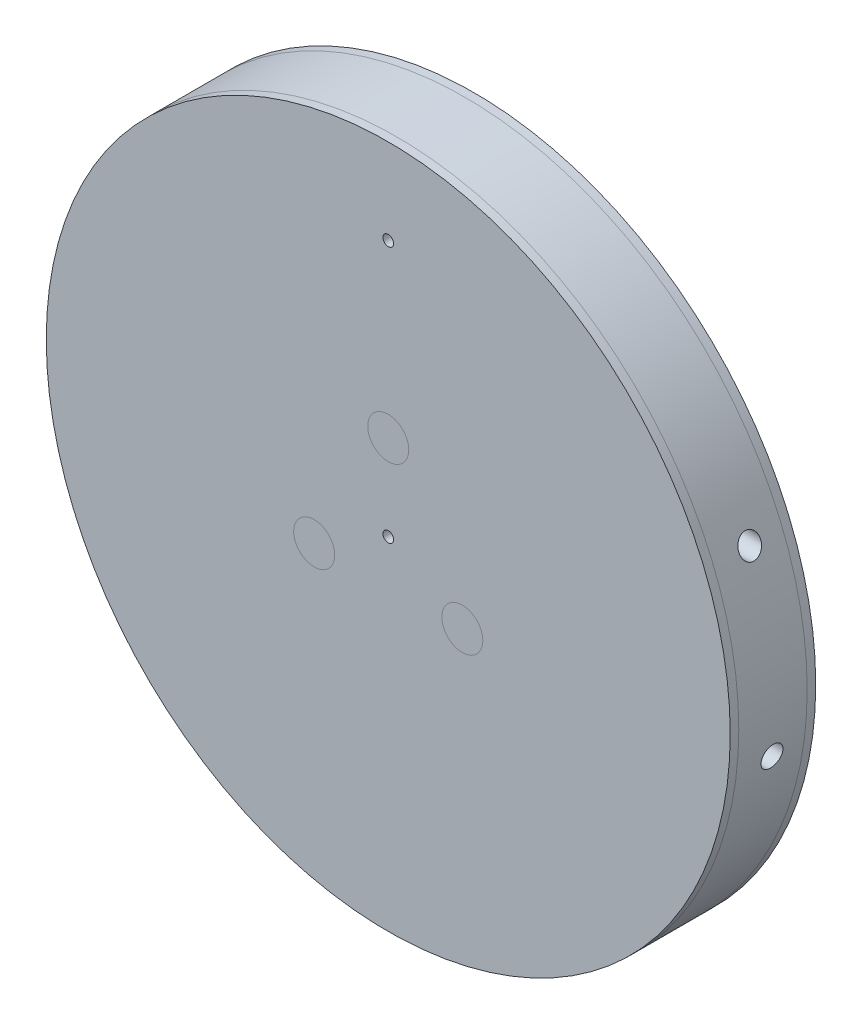
SolidWorks part; units mm, degrees
ref_plane "Front Plane" through (0, 0, 0) normal (0, 0, 1) x (1, 0, 0)
ref_plane "Top Plane" through (0, 0, 0) normal (0, 1, 0) x (1, 0, 0)
ref_plane "Right Plane" through (0, 0, 0) normal (1, 0, 0) x (0, 0, -1)
sketch "Sketch1" plane through (0, 0, 0) normal (0, 0, 1) x (1, 0, 0)
  circle A0 centre (0, 0) radius 100
  dimension "D1" = 200
extrude "Boss-Extrude1" add sketch "Sketch1" along normal blind 25
sketch "Sketch2" plane through (0, 0, 0) normal (1, 0, 0) x (0, 0, -1)
  line L0 (-25, 100) -> (-25, -100) construction
  circle A0 centre (-12, 37.5) radius 3.2
  dimension "D1" = 6.4
  dimension "D2" = 13
  dimension "D3" = 37.5
extrude "Cut-Extrude1" cut sketch "Sketch2" against normal blind 55.2975 and the other way through all
sketch "Sketch3" plane through (0, 0, 0) normal (1, 0, 0) x (0, 0, -1)
  circle A0 centre (-12, -12.5) radius 3.2
  dimension "D1" = 6.4
  dimension "D2" = 12
  dimension "D3" = 12.5
extrude "Cut-Extrude2" cut sketch "Sketch3" along normal through all and the other way blind 54.7843
sketch "Sketch4" plane through (0, 0, 0) normal (1, 0, 0) x (0, 0, -1)
  line L0 (0, -100) -> (0, 100) construction
  circle A0 centre (-12, 12.5) radius 3.2
  dimension "D2" = 6.4
  dimension "D1" = 12
  dimension "D3" = 12.5
extrude "Cut-Extrude3" cut sketch "Sketch4" against normal through all and the other way blind 54.7843
sketch "Sketch5" plane through (0, 0, 0) normal (1, 0, 0) x (0, 0, -1)
  line L0 (0, -100) -> (0, 100) construction
  circle A0 centre (-12, -37.5) radius 3.2
  dimension "D2" = 6.4
  dimension "D1" = 12
  dimension "D3" = 37.5
extrude "Cut-Extrude4" cut sketch "Sketch5" against normal through all and the other way blind 55.2975
sketch "Sketch6" plane through (0, 0, 0) normal (0, 0, -1) x (-1, 0, 0)
  circle A0 centre (0, 0) radius 50
  dimension "D1" = 100
extrude "Boss-Extrude5" add sketch "Sketch6" along normal blind 0.1 separate body
sketch "Sketch8" plane through (0, 0, -0.1) normal (0, 0, -1) x (-1, 0, 0)
  circle A1 centre (0, 0) radius 50
  circle A2 centre (0, 0) radius 50
  dimension "D1" = 0
extrude "Boss-Extrude6" add sketch "Sketch8" along normal blind 0.525 separate body
ref_plane "Bottom Plane" through (0, 0, 25) normal (0, 0, 1) x (1, 0, 0)
sketch "Sketch10" plane through (0, 0, 25) normal (0, 0, 1) x (1, 0, 0)
  circle A0 centre (0, 0) radius 1.55
  dimension "D1" = 3.1
extrude "Cut-Extrude5" cut sketch "Sketch10" against normal blind 21
sketch "Sketch11" plane through (0, 0, 25) normal (0, 0, 1) x (1, 0, 0)
  circle A0 centre (0, 75) radius 1.55
  point P2 (0, 0)
  point P5 (0, 0)
  point P6 (0, 0)
  dimension "D1" = 3.1
  dimension "D2" = 75
extrude "Cut-Extrude6" cut sketch "Sketch11" against normal blind 21
ref_plane "Ref1" through (50, 0, 0) normal (1, 0, 0) x (0, 0, -1)
ref_plane "Ref2" through (-50, 0, 0) normal (1, 0, 0) x (0, 0, -1)
ref_plane "BandRef1" through (0, 0, 2.5) normal (0, 0, 1) x (1, 0, 0)
ref_plane "BandRef2" through (0, 0, 22.5) normal (0, 0, 1) x (1, 0, 0)
split line "Split Line3"
split line "Split Line4"
sketch "Sketch12" plane through (0, 0, 25) normal (0, 0, 1) x (1, 0, 0)
  circle A0 centre (-21.6506, -12.5) radius 6
  circle A1 centre (0, 25) radius 6
  circle A2 centre (21.6506, -12.5) radius 6
  dimension "D1" = 12
  dimension "D4" = 12
  dimension "D5" = 12
  dimension "D2" = 25
  dimension "D3" = 25
  dimension "D6" = 25
split line "Split Line5"
sketch "Sketch13" plane through (0, 0, 0) normal (0, 0, 1) x (1, 0, 0)
  circle A0 centre (0, 0) radius 50
split line "Split Line6"
